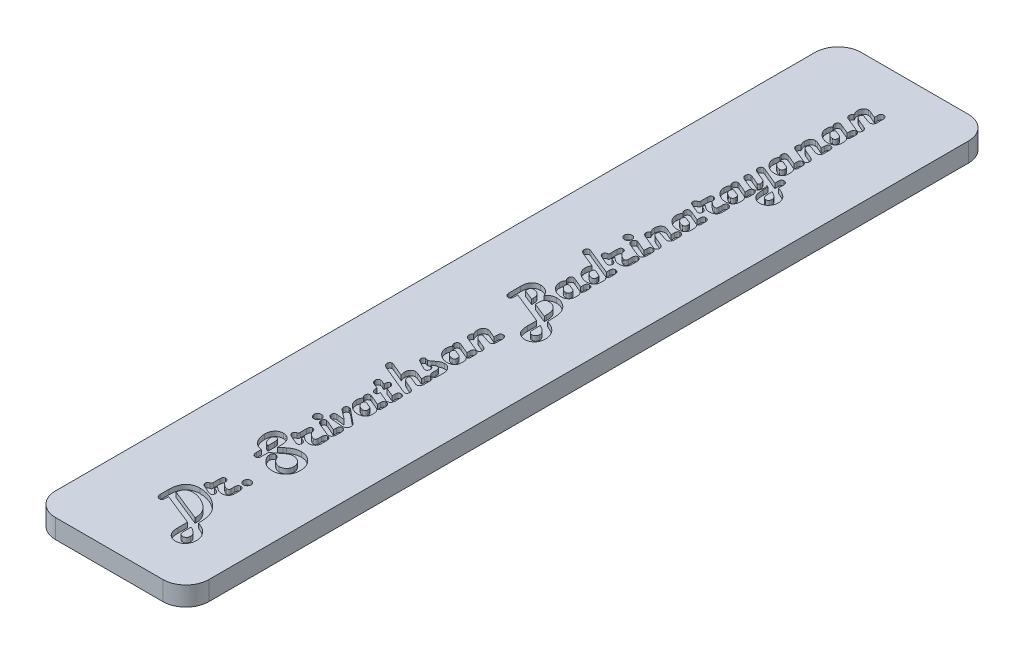
SolidWorks part; units mm, degrees
ref_plane "Front Plane" through (0, 0, 0) normal (0, 0, 1) x (1, 0, 0)
ref_plane "Top Plane" through (0, 0, 0) normal (0, 1, 0) x (1, 0, 0)
ref_plane "Right Plane" through (0, 0, 0) normal (1, 0, 0) x (0, 0, -1)
sketch "Sketch1" plane through (0, 0, 0) normal (0, 0, 1) x (1, 0, 0)
  line L0 (0, 1.5875) -> (0, -1.5875)
  line L1 (-12.7, 0) -> (12.7, 0) construction
  point P6 (0, 0)
  dimension "Width" = 25.4
  dimension "Thk" = 3.175
sketch "Sketch2" plane through (0, 0, 0) normal (1, 0, 0) x (0, 0, -1)
  line L0 (66.675, 0) -> (-66.675, 0)
  point P4 (0, 0)
  dimension "Length" = 133.35
sketch "Sketch3" plane through (0, 0, 0) normal (0, 0, 1) x (1, 0, 0)
  line L1 (12.7, 1.5875) -> (-12.7, 1.5875)
  line L2 (12.7, 1.5875) -> (12.7, -1.5875)
  line L3 (12.7, -1.5875) -> (-12.7, -1.5875)
  line L4 (-12.7, 1.5875) -> (-12.7, -1.5875)
  line L5 (12.7, 1.5875) -> (-12.7, -1.5875) construction
  line L6 (12.7, -1.5875) -> (-12.7, 1.5875) construction
  point P0 (0, 0)
extrude "Boss-Extrude1" add sketch "Sketch3" along normal up to vertex (66.675 mm away) and the other way up to vertex (66.675 mm away) up to point (0, 0, 66.675) other way up to point (0, 0, -66.675)
sketch "Sketch5" plane through (0, 1.5875, 0) normal (0, 1, 0) x (1, 0, 0)
  line L2 (9.652, -66.675) -> (-9.398, -66.675) construction
  line L3 (-12.7, -63.5025) -> (-12.7, 63.627) construction
  line L12 (12.7, -66.675) -> (12.7, 66.675)
  line L13 (12.7, 66.675) -> (-12.7, 66.675)
  line L14 (-12.7, 66.675) -> (-12.7, -66.675)
  line L15 (-12.7, -66.675) -> (12.7, -66.675)
  line L16 (12.7, -62.865) -> (12.7, 62.865)
  line L17 (8.89, 66.675) -> (-8.89, 66.675)
  line L18 (-12.7, 62.865) -> (-12.7, -62.865)
  line L19 (-8.89, -66.675) -> (8.89, -66.675)
  arc A8 (12.7, 62.865) -> (8.89, 66.675) centre (8.89, 62.865) ccw
  arc A9 (-8.89, 66.675) -> (-12.7, 62.865) centre (-8.89, 62.865) ccw
  arc A10 (12.7, -62.865) -> (8.89, -66.675) centre (8.89, -62.865) cw
  arc A11 (-8.89, -66.675) -> (-12.7, -62.865) centre (-8.89, -62.865) cw
  dimension "D2" = 3.81
  dimension "D1" = 0
extrude "Cut-Extrude2" cut sketch "Sketch5" against normal through all flip side to cut
sketch "Sketch4" plane through (0, 1.5875, 0) normal (0, 1, 0) x (1, 0, 0)
  line L0 (0, 0) -> (2.54, 0) construction
  line L1 (2.54, -66.675) -> (2.54, 66.675) construction
  line L2 (8.89, 66.675) -> (-8.89, 66.675) construction
  text T0 "Dr. Srivathsan Badrinarayanan" font "Harlow Solid Italic" height in points 20
  point P8 (2.54, 0)
  dimension "D1" = 2.54
extrude "Cut-Extrude1" cut sketch "Sketch4" against normal blind 0.7937
